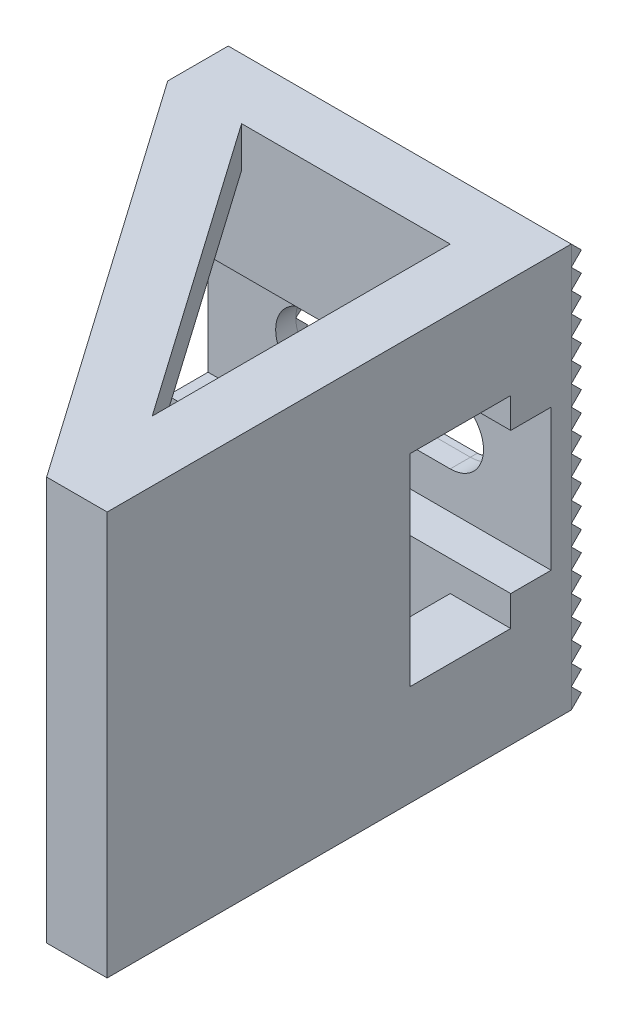
SolidWorks part; units mm, degrees
ref_plane "Front Plane" through (0, 0, 0) normal (0, 0, 1) x (1, 0, 0)
ref_plane "Top Plane" through (0, 0, 0) normal (0, 1, 0) x (1, 0, 0)
ref_plane "Right Plane" through (0, 0, 0) normal (1, 0, 0) x (0, 0, -1)
sketch "Sketch1" plane through (0, 0, 0) normal (0, 0, 1) x (1, 0, 0)
  line L1 (8.5, -10) -> (-8.5, -10)
  line L2 (8.5, -10) -> (8.5, 10)
  line L3 (8.5, 10) -> (-8.5, 10)
  line L4 (-8.5, -10) -> (-8.5, 10)
  line L5 (8.5, -10) -> (-8.5, 10) construction
  line L6 (8.5, 10) -> (-8.5, -10) construction
  point P0 (0, 0)
  dimension "D1" = 17
  dimension "D2" = 20
extrude "Boss-Extrude1" add sketch "Sketch1" along normal blind 3
sketch "Sketch2" plane through (0, 0, 3) normal (0, 0, 1) x (1, 0, 0)
  line L0 (-8.5, -10) -> (8.5, -10) construction
  line L1 (8.5, 10) -> (5.5, 10)
  line L2 (8.5, 10) -> (8.5, -10)
  line L3 (8.5, -10) -> (5.5, -10)
  line L4 (5.5, 10) -> (5.5, -10)
  dimension "D1" = 3
extrude "Boss-Extrude2" add sketch "Sketch2" along normal blind 20
sketch "Sketch3" plane through (0, -10, 0) normal (0, -1, 0) x (1, 0, 0)
  line L0 (5.5, 23) -> (-8.5, 3)
  line L1 (-8.5, 3) -> (-4.838, 3)
  line L2 (-8.5, 3) -> (5.5, 3) construction
  line L3 (-4.838, 3) -> (5.5, 17.7686)
  line L4 (5.5, 23) -> (5.5, 3) construction
  line L5 (5.5, 17.7686) -> (5.5, 23)
  dimension "D1" = 3
extrude "Boss-Extrude3" add sketch "Sketch3" against normal blind 2
extrude "Boss-Extrude4" add sketch "Sketch3<2>" along normal blind 2 from offset 20 offset against normal yes
sketch "Sketch3<2>" plane through (0, -10, 0) normal (0, -1, 0) x (1, 0, 0) same geometry as "Sketch3"
sketch "Sketch4" plane through (5.5, 0, 0) normal (-1, 0, 0) x (0, 0, 1)
  line L0 (3, 10) -> (3, -10) construction
  line L1 (3, 5) -> (8, 5)
  line L2 (3, 5) -> (3, -5)
  line L3 (3, -5) -> (8, -5)
  line L4 (8, 5) -> (8, -5)
  line L5 (23, 10) -> (3, 10) construction
  dimension "D1" = 10
  dimension "D2" = 5
  dimension "D3" = 5
extrude "Cut-Extrude1" cut sketch "Sketch4" against normal blind 12
sketch "Sketch5" plane through (8.5, 0, 0) normal (1, 0, 0) x (0, 0, -1)
  line L0 (0, 10) -> (0.5, 9.5)
  line L1 (0.5, 9.5) -> (0, 9)
  line L2 (0, -10) -> (0, 10) construction
  line L3 (0, 10) -> (0, 9)
  line L4 (0, 9) -> (0, 8)
  line L5 (0.5, 8.5) -> (0, 8)
  line L6 (0, 9) -> (0.5, 8.5)
  line L7 (0, 8) -> (0, 7)
  line L8 (0.5, 7.5) -> (0, 7)
  line L9 (0, 8) -> (0.5, 7.5)
  line L10 (0, 7) -> (0, 6)
  line L11 (0.5, 6.5) -> (0, 6)
  line L12 (0, 7) -> (0.5, 6.5)
  line L13 (0, 6) -> (0, 5)
  line L14 (0.5, 5.5) -> (0, 5)
  line L15 (0, 6) -> (0.5, 5.5)
  line L16 (0, 5) -> (0, 4)
  line L17 (0.5, 4.5) -> (0, 4)
  line L18 (0, 5) -> (0.5, 4.5)
  line L19 (0, 4) -> (0, 3)
  line L20 (0.5, 3.5) -> (0, 3)
  line L21 (0, 4) -> (0.5, 3.5)
  line L22 (0, 3) -> (0, 2)
  line L23 (0.5, 2.5) -> (0, 2)
  line L24 (0, 3) -> (0.5, 2.5)
  line L25 (0, 2) -> (0, 1)
  line L26 (0.5, 1.5) -> (0, 1)
  line L27 (0, 2) -> (0.5, 1.5)
  line L28 (0, 1) -> (0, 0)
  line L29 (0.5, 0.5) -> (0, 0)
  line L30 (0, 1) -> (0.5, 0.5)
  line L31 (0, 0) -> (0, -1)
  line L32 (0.5, -0.5) -> (0, -1)
  line L33 (0, 0) -> (0.5, -0.5)
  line L34 (0, -1) -> (0, -2)
  line L35 (0.5, -1.5) -> (0, -2)
  line L36 (0, -1) -> (0.5, -1.5)
  line L37 (0, -2) -> (0, -3)
  line L38 (0.5, -2.5) -> (0, -3)
  line L39 (0, -2) -> (0.5, -2.5)
  line L40 (0, -3) -> (0, -4)
  line L41 (0.5, -3.5) -> (0, -4)
  line L42 (0, -3) -> (0.5, -3.5)
  line L43 (0, -4) -> (0, -5)
  line L44 (0.5, -4.5) -> (0, -5)
  line L45 (0, -4) -> (0.5, -4.5)
  line L46 (0, -5) -> (0, -6)
  line L47 (0.5, -5.5) -> (0, -6)
  line L48 (0, -5) -> (0.5, -5.5)
  line L49 (0, -6) -> (0, -7)
  line L50 (0.5, -6.5) -> (0, -7)
  line L51 (0, -6) -> (0.5, -6.5)
  line L52 (0, -7) -> (0, -8)
  line L53 (0.5, -7.5) -> (0, -8)
  line L54 (0, -7) -> (0.5, -7.5)
  line L55 (0, -8) -> (0, -9)
  line L56 (0.5, -8.5) -> (0, -9)
  line L57 (0, -8) -> (0.5, -8.5)
  line L58 (0, -9) -> (0, -10)
  line L59 (0.5, -9.5) -> (0, -10)
  line L60 (0, -9) -> (0.5, -9.5)
  line M8 (0, -10) -> (0, 10)
  dimension "D1" = 1
  dimension "D2" = 90
  dimension "D3" = 20
extrude "Boss-Extrude9" add sketch "Sketch5" against normal up to surface (17 mm away) separate body contours L60 L59 M8 | L33 L32 M8 | L30 L29 M8 | L27 L26 M8 | L55 L56 L57 | L52 L53 L54 | L49 L50 L51 | L46 L47 L48 | L43 L44 L45 | L40 L41 L42 | L37 L38 L39 | L34 L35 L36 | L22 L23 L24 | L19 L20 L21 | L16 L17 L18 | L13 L14 L15 | L10 L11 L12 | L7 L8 L9 | L4 L5 L6 | L3 L1 L0 region at (8.5, -9.5, -0.1667) region at (8.5, -0.5, -0.1667) region at (8.5, 0.5, -0.1667) region at (8.5, 1.5, -0.1667) up to face at (-8.5, 0, 2)
sketch "Sketch6" plane through (0, 0, 3) normal (0, 0, 1) x (1, 0, 0)
  line L0 (3.5, 0) -> (-3.5, 0) construction
  line L1 (3.5, -1.65) -> (-3.5, -1.65)
  line L2 (3.5, 1.65) -> (-3.5, 1.65)
  arc A0 (3.5, -1.65) -> (3.5, 1.65) centre (3.5, 0) ccw
  arc A1 (-3.5, 1.65) -> (-3.5, -1.65) centre (-3.5, 0) ccw
  point P2 (0, 0)
  dimension "D1" = 3.3
  dimension "D2" = 7
extrude "Cut-Extrude2" cut sketch "Sketch6" against normal blind 10
sketch "Sketch8" plane through (0, 0, 3) normal (0, 0, 1) x (1, 0, 0)
  line L0 (-8.5, 8) -> (-8.5, -8) construction
  line L1 (8.5, -3.5) -> (-8.5, -3.5)
  line L2 (8.5, -3.5) -> (8.5, 3.5)
  line L3 (8.5, 3.5) -> (-8.5, 3.5)
  line L4 (-8.5, -3.5) -> (-8.5, 3.5)
  line L5 (8.5, -3.5) -> (-8.5, 3.5) construction
  line L6 (8.5, 3.5) -> (-8.5, -3.5) construction
  point P0 (0, 0)
  dimension "D1" = 7
extrude "Cut-Extrude3" cut sketch "Sketch8" against normal blind 2
